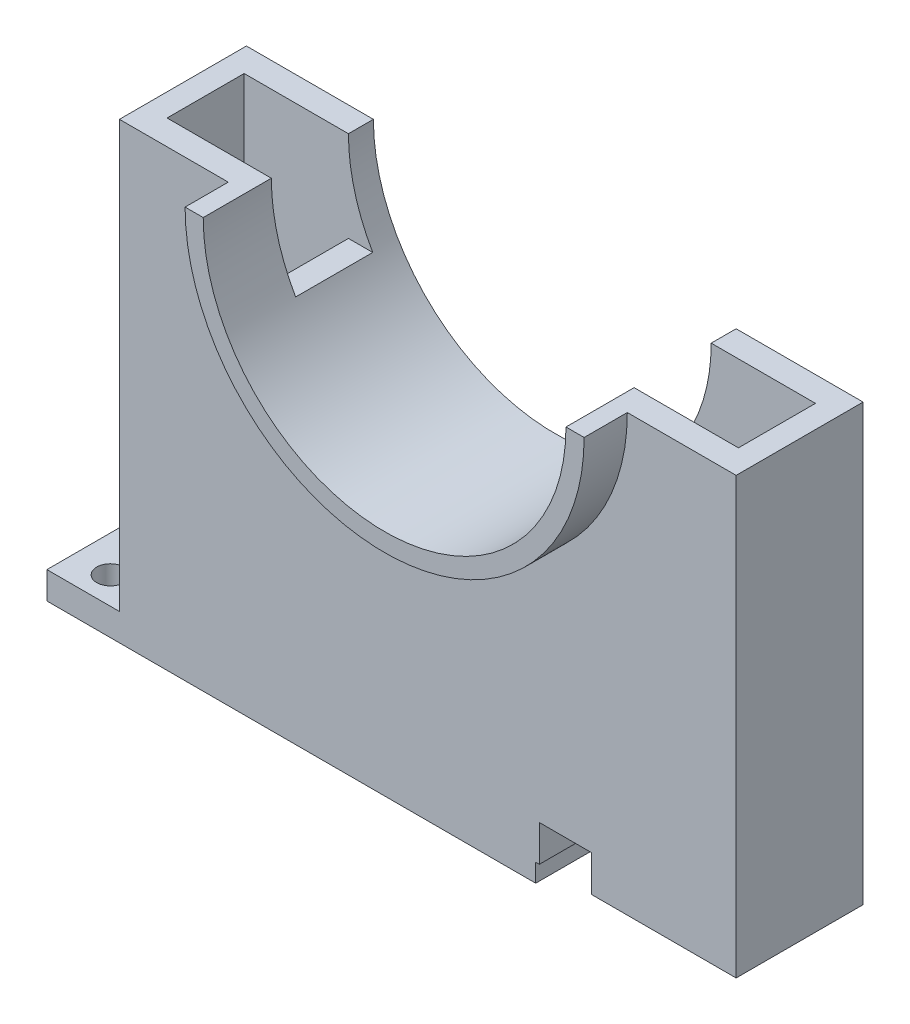
SolidWorks part; units mm, degrees
ref_plane "Front Plane" through (0, 0, 0) normal (0, 0, 1) x (1, 0, 0)
ref_plane "Top Plane" through (0, 0, 0) normal (0, 1, 0) x (1, 0, 0)
ref_plane "Right Plane" through (0, 0, 0) normal (1, 0, 0) x (0, 0, -1)
sketch "Sketch1" plane through (0, 0, 0) normal (0, 0, 1) x (1, 0, 0)
  line L0 (0, 0) -> (0, 3)
  line L1 (0, 3) -> (8, 3)
  line L2 (0, 0) -> (76, 0)
  line L3 (76, 0) -> (76, 50)
  line L4 (8, 3) -> (8, 50)
  line L5 (8, 50) -> (22, 50)
  line L6 (76, 50) -> (62, 50)
  arc A1 (62, 50) -> (22, 50) centre (42, 50) cw
  dimension "D1" = 14
  dimension "D2" = 20
  dimension "D3" = 3
  dimension "D4" = 50
  dimension "D5" = 8
extrude "Boss-Extrude1" add sketch "Sketch1" along normal blind 14
sketch "Sketch2" plane through (0, 0, 0) normal (0, -1, 0) x (1, 0, 0)
  line L0 (42, 14) -> (42, 0) construction
  line L1 (0, 14) -> (76, 14) construction
  line L2 (0, 0) -> (76, 0) construction
  line L3 (62, 14) -> (22, 14) construction
  line L4 (73.5, 11.25) -> (62, 11.25)
  line L5 (62, 11.25) -> (62, 2.75)
  line L6 (62, 2.75) -> (73.5, 2.75)
  line L7 (73.5, 2.75) -> (73.5, 11.25)
  line L10 (76, 14) -> (76, 0) construction
  line L11 (22, 2.75) -> (10.5, 2.75)
  line L12 (22, 11.25) -> (22, 2.75)
  line L13 (10.5, 11.25) -> (22, 11.25)
  line L14 (10.5, 2.75) -> (10.5, 11.25)
  point P14 (76, 7)
  point P15 (73.5, 7)
  dimension "D1" = 11.5
  dimension "D2" = 8.5
  dimension "D3" = 2.5
extrude "Cut-Extrude1" cut sketch "Sketch2" against normal up to surface (50 mm away) up to face at (15, 50, 7)
sketch "Sketch3" plane through (0, 3, 0) normal (0, 1, 0) x (1, 0, 0)
  line L0 (4, -3) -> (4, -11) construction
  line L1 (0, -14) -> (0, 0) construction
  line L4 (8, -14) -> (0, -14) construction
  circle A0 centre (4, -3) radius 1.5
  circle A1 centre (4, -11) radius 1.5
  point P7 (4, -14)
  point P10 (0, -7)
  point P11 (4, -7)
  dimension "D1" = 3
  dimension "D2" = 3
  dimension "D3" = 8
extrude "screw holes" cut sketch "Sketch3" against normal up to surface (3 mm away) up to face at (67.75, 0, 7)
sketch "Sketch4" plane through (0, 50, 0) normal (0, 1, 0) x (1, 0, 0)
  line L0 (8, -14) -> (76, -14) construction
  line L1 (10.5, -11.25) -> (73.5, -11.25)
  line L5 (73.5, -2.75) -> (73.5, -11.25)
  line L9 (10.5, -2.75) -> (10.5, -11.25)
  line L10 (10.5, -2.75) -> (73.5, -2.75)
  line L11 (10.5, -2.75) -> (10.5, -11.25) construction
extrude "Cut-Extrude2" cut sketch "Sketch4" against normal blind 10
sketch "Sketch5" plane through (0, 0, 0) normal (0, 0, -1) x (-1, 0, 0)
  line L0 (-76, 0) -> (-76, 2)
  line L1 (-76, 0) -> (-76, 50) construction
  line L2 (-76, 2) -> (-53.9, 2)
  line L3 (-53.9, 2) -> (-53.9, 0)
  line L4 (0, 0) -> (-76, 0) construction
  line L5 (-53.9, 0) -> (-76, 0)
  dimension "D1" = 2
  dimension "D2" = 22.1
extrude "Cut-Extrude3" cut sketch "Sketch5" against normal up to surface (14 mm away) up to face at (31.5, 23.25, 14)
sketch "Sketch6" plane through (0, 0, 14) normal (0, 0, 1) x (1, 0, 0)
  line L0 (54.295, 2) -> (60.045, 2)
  line L2 (76, 2) -> (53.9, 2) construction
  line L3 (53.9, 2) -> (53.9, 0) construction
  line L4 (60.045, 2) -> (60.045, 6)
  line L5 (60.045, 6) -> (54.295, 6)
  line L6 (54.295, 6) -> (54.295, 2)
  point P6 (57.17, 2)
  dimension "D1" = 5.75
  dimension "D2" = 3.27
  dimension "D3" = 4
extrude "Cut-Extrude4" cut sketch "Sketch6" against normal blind 8
sketch "Sketch7" plane through (0, 0, 14) normal (0, 0, 1) x (1, 0, 0)
  line L0 (22, 50) -> (20, 50)
  line L1 (22, 50) -> (8, 50) construction
  line L2 (62, 50) -> (64, 50)
  line L3 (76, 50) -> (62, 50) construction
  arc A0 (22, 50) -> (62, 50) centre (42, 50) ccw
  arc A1 (20, 50) -> (64, 50) centre (42, 50) ccw
  dimension "D1" = 2
  dimension "D2" = 2
extrude "Boss-Extrude2" add sketch "Sketch7" along normal blind 4.7625
